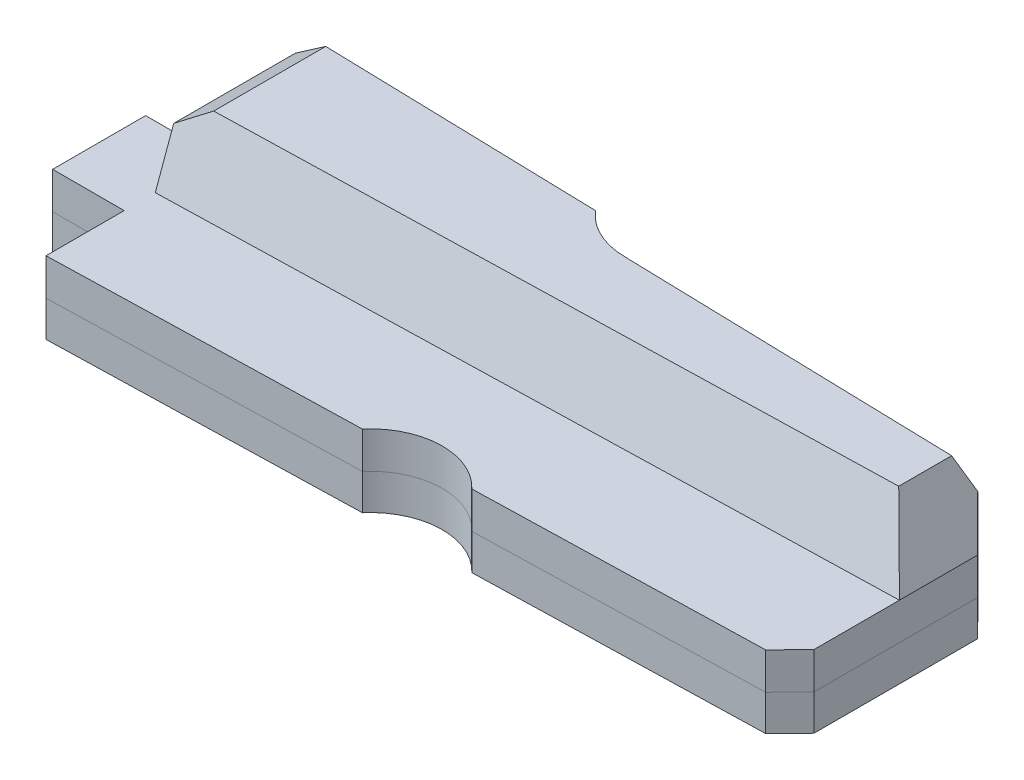
SolidWorks part; units mm, degrees
ref_plane "Front Plane" through (0, 0, 0) normal (0, 0, 1) x (1, 0, 0)
ref_plane "Top Plane" through (0, 0, 0) normal (0, 1, 0) x (1, 0, 0)
ref_plane "Right Plane" through (0, 0, 0) normal (1, 0, 0) x (0, 0, -1)
sketch "Sketch1" plane through (0, 0, 0) normal (0, 1, 0) x (1, 0, 0)
  line L0 (-14.914, 10.7961) -> (-14.914, -10.7339)
  line L1 (-14.914, -10.7339) -> (57.586, -8.8214)
  line L2 (57.586, -8.8214) -> (57.586, 8.8786)
  line L3 (57.586, 8.8786) -> (-14.914, 10.7961)
  dimension "D1" = 21.53
  dimension "D2" = 17.7
  dimension "D3" = 72.5
  dimension "D4" = 88.485
extrude "Boss-Extrude1" add sketch "Sketch1" along normal blind 6.08
sketch "Sketch2" plane through (0, 6.08, 0) normal (0, 1, 0) x (1, 0, 0)
  line L2 (-13.064, 10.7961) -> (-13.064, -10.7339)
  line L3 (-13.064, 10.7472) -> (-13.064, -1.5219)
  line L5 (-15.1556, -1.5771) -> (57.3444, 0.3354)
  line L6 (-13.064, -1.5219) -> (57.586, 0.3418)
  line L8 (57.586, 8.8786) -> (-14.914, 10.7961)
  line L9 (57.586, 8.8786) -> (-13.064, 10.7472)
  line L11 (57.586, -8.8214) -> (57.586, 8.8786)
  line L12 (57.586, 0.3418) -> (57.586, 8.8786)
  dimension "D1" = 1.85
  dimension "D2" = 9.16
  dimension "D3" = 0
  dimension "D4" = 0
extrude "Boss-Extrude2" add sketch "Sketch2" along normal blind 6.09
ref_plane "Plane1" through (0.0789, 1.0895, 2.9922) normal (0.0248, 0.342, 0.9394) x (0.9997, 0, -0.0264)
ref_axis "Axis1" through (-13.064, 12.17, -0.6954) along (0.9997, 0, -0.0264)
sketch "Sketch4" plane through (0.0789, 1.0895, 2.9922) normal (0.0248, 0.342, 0.9394) x (0.9997, 0, -0.0264)
  line L2 (-13.0996, 5.3108) -> (57.5749, 5.3108)
  line L3 (-13.0996, 5.3108) -> (57.8001, 5.3108)
  line L5 (-13.0996, 11.0335) -> (-13.0996, 5.3108)
  line L6 (-13.0996, 14.6247) -> (-13.0996, 5.3108)
  line L7 (-13.0996, 14.6247) -> (57.8001, 14.6247)
  line L10 (57.8001, 13.9523) -> (57.8001, 2.5162) construction
  line L11 (57.8001, 13.9523) -> (57.8001, 2.5162)
  line L12 (57.8001, 14.6247) -> (57.8001, 5.3108)
  dimension "D1" = 0
  dimension "D2" = 0
  dimension "D3" = 0
extrude "Cut-Extrude4" cut sketch "Sketch4" along normal blind 13.09 contours L3 L12 L7 L6
ref_plane "Plane2" through (52.8037, 19.219, 0) normal (0.9397, 0.342, 0) x (0, 0, -1)
sketch "Sketch5" plane through (52.8037, 19.219, 0) normal (0.9397, 0.342, 0) x (0, 0, -1)
  line L1 (-14.2418, -13.9822) -> (-14.2418, -1.7479)
  line L2 (-8.8214, -13.9822) -> (0.3418, -13.9822)
  line L3 (-14.2418, -13.9822) -> (15.0642, -13.9822)
  line L4 (-14.2418, -1.7479) -> (15.0642, -1.7479)
  line L5 (15.0642, -1.7479) -> (15.0642, -13.9822)
  dimension "D1" = 0
extrude "Cut-Extrude5" cut sketch "Sketch5" along normal blind 19.09
sketch "Sketch6" plane through (0, 0, 0) normal (0, -1, 0) x (1, 0, 0)
  line L0 (-14.914, 10.7339) -> (-14.914, 8.7339)
  line L1 (-14.914, -10.7961) -> (-14.914, 10.7339) construction
  line L2 (-14.914, 8.7339) -> (-12.914, 10.6811)
  line L3 (-14.914, 10.7339) -> (57.586, 8.8214) construction
  line L4 (-12.914, 10.6811) -> (-14.914, 10.7339)
  line L5 (-14.914, -10.7961) -> (-12.914, -10.7432)
  line L6 (57.586, -8.8786) -> (-14.914, -10.7961) construction
  line L7 (-12.914, -10.7432) -> (-14.914, -8.7961)
  line L8 (-14.914, -8.7961) -> (-14.914, -10.7961)
  line L9 (55.5866, 8.8741) -> (57.586, 8.8214)
  line L10 (57.586, 8.8214) -> (57.586, 6.8214)
  line L11 (57.586, 8.8214) -> (57.586, -8.8786) construction
  line L12 (57.586, 6.8214) -> (55.5866, 8.8741)
  line L13 (57.586, -8.8786) -> (57.586, -6.8786)
  line L14 (57.586, -6.8786) -> (55.586, -8.9315)
  line L15 (55.586, -8.9315) -> (57.586, -8.8786)
  line L16 (27.216, 19.304) -> (27.216, -14.3897) construction
  circle A1 centre (27.216, 13.6239) radius 6
  circle A2 centre (27.216, -13.6832) radius 6
  dimension "D11" = 12
  dimension "D12" = 12
  dimension "D1" = 2
  dimension "D2" = 2
  dimension "D3" = 2
  dimension "D4" = 2
  dimension "D5" = 2
  dimension "D6" = 2
  dimension "D7" = 2
  dimension "D8" = 2
  dimension "D9" = 42.13
  dimension "D10" = 4
  dimension "D13" = 4
extrude "Cut-Extrude6" cut sketch "Sketch6" against normal through all
ref_plane "Plane3" through (0, 7.78, 0) normal (0, 1, 0) x (1, 0, 0)
ref_axis "Axis2" through (360.074, 7.78, -0.8784) along (-0.9997, 0, -0.0264)
ref_plane "Plane4" through (0.3053, 5.2601, -11.542) normal (0.0241, 0.4146, -0.9097) x (-0.9997, 0.01, -0.0219)
sketch "Sketch7" plane through (0.3053, 5.2601, -11.542) normal (0.0241, 0.4146, -0.9097) x (-0.9997, 0.01, -0.0219)
  line L0 (-26.9217, 7.8879) -> (-26.9217, 3.0644)
  line L1 (-359.8729, 6.7147) -> (-60.2731, 3.43) construction
  line L2 (-26.9217, 3.0644) -> (-63.5754, 3.4662)
  line L3 (-63.5754, 3.4662) -> (-63.5754, 10.3897)
  line L4 (-63.5754, 10.3897) -> (-26.9217, 9.9878)
  line L5 (-26.9217, 9.9878) -> (-26.9217, 7.8879)
  ellipse E0 centre (-26.7871, 5.3996) end of major axis (-20.7874, 5.3339) minor radius 2.4875 (-22.297, 7.0089) -> (-31.2408, 7.1069) ccw construction
extrude "Cut-Extrude7" cut sketch "Sketch7" along normal blind 11.09
ref_plane "Cut surface" through (-3.214, 0, 0) normal (-1, 0, 0) x (0, 0, 1)
sketch "Sketch10" plane through (-3.214, 0, 0) normal (-1, 0, 0) x (0, 0, 1)
  line L1 (-17.6293, 15.2246) -> (18.4681, 15.2246)
  line L2 (-17.6293, 15.2246) -> (-17.6293, -7.7626)
  line L3 (-17.6293, -7.7626) -> (18.4681, -7.7626)
  line L4 (18.4681, 15.2246) -> (18.4681, -7.7626)
extrude "Cut-Extrude11" cut sketch "Sketch10" along normal through all
sketch "Sketch12" plane through (-3.214, 0, 0) normal (-1, 0, 0) x (0, 0, 1)
  line L1 (-3.9307, 6.08) -> (3.8693, 6.08)
  line L2 (-3.9307, 6.08) -> (-3.9307, 0)
  line L3 (-3.9307, 0) -> (3.8693, 0)
  line L4 (3.8693, 6.08) -> (3.8693, 0)
  line L5 (-10.4867, 0) -> (10.4253, 0) construction
  line L6 (-0.0307, -3.669) -> (-0.0307, 11.8159) construction
  line L8 (1.2621, 6.08) -> (10.4253, 6.08) construction
  line L11 (-10.4867, 12.17) -> (-10.4867, 0) construction
  line L12 (10.4253, 0) -> (10.4253, 6.08) construction
  dimension "D1" = 7.8
  dimension "D4" = 0
extrude "Boss-Extrude4" add sketch "Sketch12" along normal blind 6
ref_plane "Plane5" through (-6.7754, 9.6763, 0) normal (-0.5736, 0.8192, 0) x (0, 0, 1)
ref_plane "Plane6" through (-5.9151, 8.4476, 0) normal (-0.5736, 0.8192, 0) x (0, 0, 1)
sketch "Sketch13" plane through (-5.9151, 8.4476, 0) normal (-0.5736, 0.8192, 0) x (0, 0, 1)
  line L1 (-13.6641, 9.5503) -> (5.0822, 9.5503)
  line L2 (-13.6641, 9.5503) -> (-13.6641, 0.4074)
  line L3 (-13.6641, 0.4074) -> (5.0822, 0.4074)
  line L4 (5.0822, 9.5503) -> (5.0822, 0.4074)
extrude "Cut-Extrude12" cut sketch "Sketch13" along normal up to next
sketch "Sketch14" plane through (0, 0, 0) normal (1, 0, 0) x (0, 0, -1)
  line L0 (17.375, 3) -> (-19.4588, 3)
  line L1 (10.4867, 0) -> (3.9307, 0) construction
  dimension "D1" = 3
split "Split1" trim tools "Sketch14" bodies to split 114 resulting bodies 115 116
